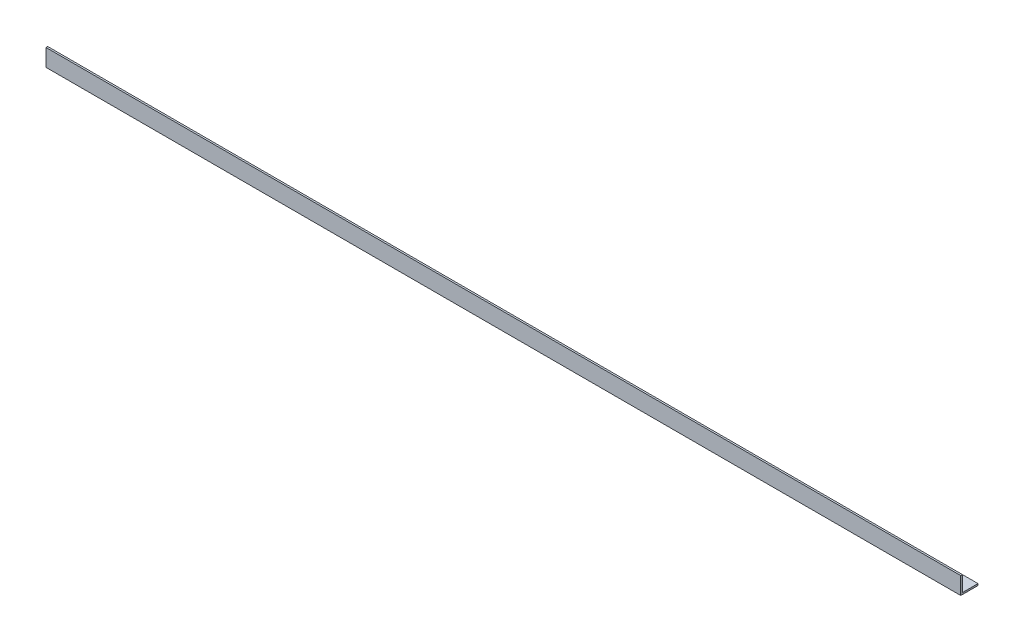
SolidWorks part; units mm, degrees
ref_plane "Спереди" through (0, 0, 0) normal (0, 0, 1) x (1, 0, 0)
ref_plane "Сверху" through (0, 0, 0) normal (0, 1, 0) x (1, 0, 0)
ref_plane "Справа" through (0, 0, 0) normal (1, 0, 0) x (0, 0, -1)
sketch "Эскиз1" plane through (0, 0, 0) normal (1, 0, 0) x (0, 0, -1)
  line L0 (0, 50) -> (0, 0)
  line L1 (0, 0) -> (50, 0)
extrude "Вытянуть-Тонкостенный1" add sketch "Эскиз1" along normal blind 2650 thin thin type one direction reverse wall 5
